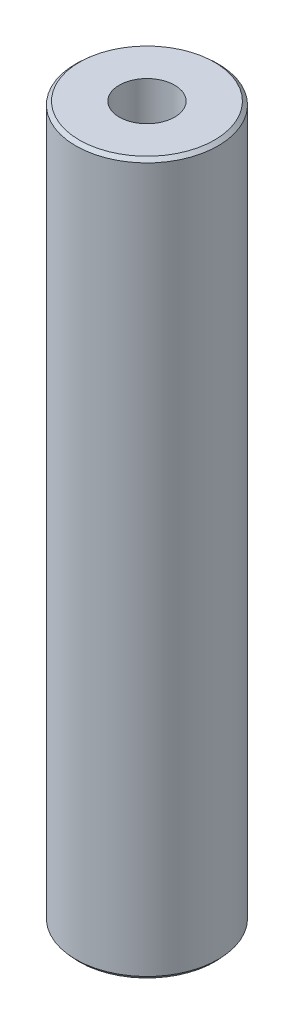
SolidWorks part; units mm, degrees
ref_plane "Front Plane" through (0, 0, 0) normal (0, 0, 1) x (1, 0, 0)
ref_plane "Top Plane" through (0, 0, 0) normal (0, 1, 0) x (1, 0, 0)
ref_plane "Right Plane" through (0, 0, 0) normal (1, 0, 0) x (0, 0, -1)
sketch "Sketch1" plane through (0, 0, 0) normal (0, 1, 0) x (1, 0, 0)
  circle A0 centre (0, 0) radius 60
  dimension "SHAFT_OD" = 120
extrude "Boss-Extrude1" add sketch "Sketch1" along normal blind 600
sketch "Sketch2" plane through (0, 0, 0) normal (0, 1, 0) x (1, 0, 0)
  circle A0 centre (0, 0) radius 23.3641
  dimension "BORE_D" = 46.7283
extrude "Cut-Extrude1" cut sketch "Sketch2" along normal through all
chamfer "Chamfer1" distance 2.7167 angle 48.293 2 edges at (0, 600, 60) (0, 0, 60) first distance on face at (0, 600, 60) first distance on face at (0, 0, 23.3641)
